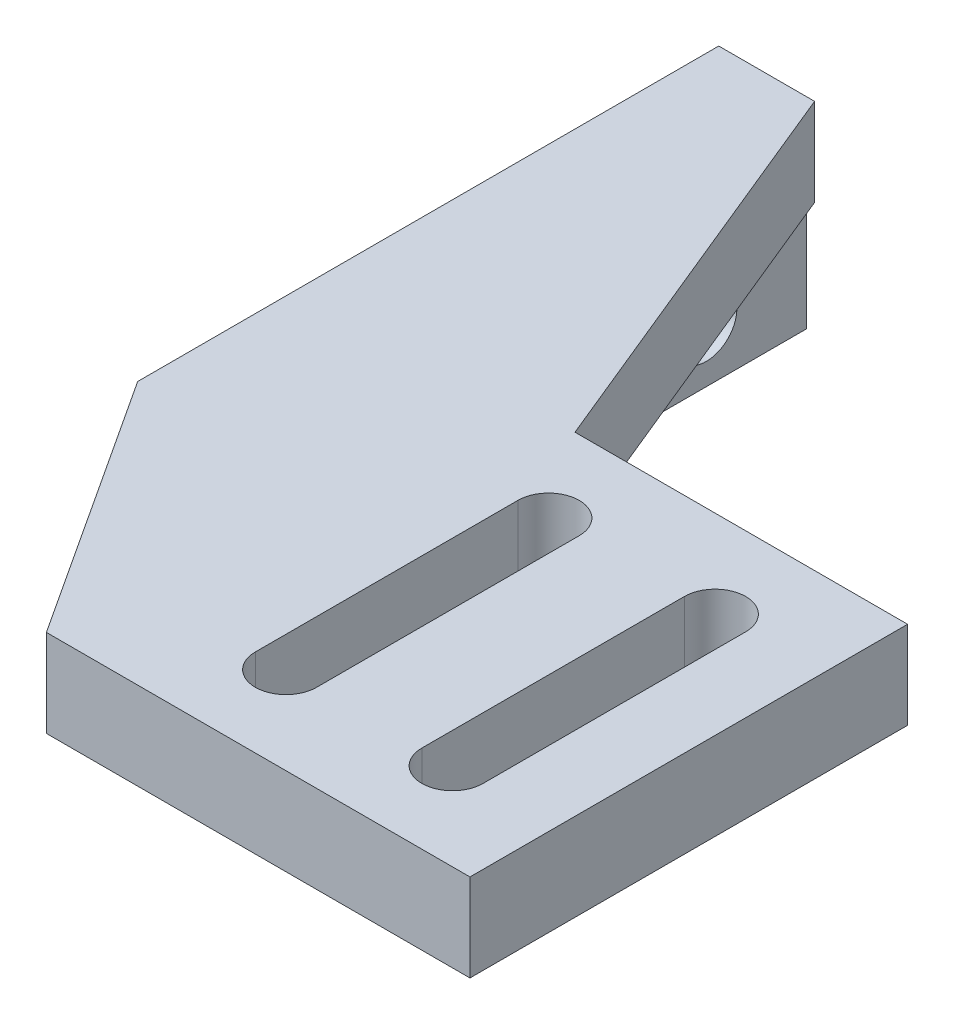
SolidWorks part; units mm, degrees
ref_plane "Piano frontale" through (0, 0, 0) normal (0, 0, 1) x (1, 0, 0)
ref_plane "Piano superiore" through (0, 0, 0) normal (0, 1, 0) x (1, 0, 0)
ref_plane "Piano destro" through (0, 0, 0) normal (1, 0, 0) x (0, 0, -1)
ref_plane "Piano1" through (0, 40, 0) normal (0, 1, 0) x (1, 0, 0)
sketch "Schizzo18" plane through (0, 40, 0) normal (0, 1, 0) x (1, 0, 0)
  line L0 (25, -16) -> (-9, -16)
  line L1 (25, -16) -> (25, 9)
  line L2 (25, 9) -> (6, 9)
  line L3 (-9, 32.2124) -> (-3.5247, 32.2124)
  line L4 (-9, -16) -> (-9, 32.2124)
  line L5 (-3.5247, 32.2124) -> (6, 9)
  line L6 (19, -16) -> (19, 9) construction
  line L7 (-9, -28.4145) -> (-9, 27.2974) construction
  line L8 (29.4558, 9) -> (-19.1855, 9) construction
  line L9 (25, -28.4145) -> (25, 27.2974) construction
  line L10 (29.4558, -16) -> (-19.1855, -16) construction
  line L11 (25, -11) -> (-9, -11) construction
  line L12 (25, 4) -> (-9, 4) construction
  line L13 (19, -11) -> (19, 4) construction
  line L14 (17.25, -11) -> (17.25, 4)
  line L15 (20.75, -11) -> (20.75, 4)
  line L16 (9.4906, -11) -> (9.4906, 4) construction
  line L17 (7.7406, -11) -> (7.7406, 4)
  line L18 (11.2406, -11) -> (11.2406, 4)
  arc A0 (17.25, -11) -> (20.75, -11) centre (19, -11) ccw
  arc A1 (20.75, 4) -> (17.25, 4) centre (19, 4) ccw
  arc A2 (7.7406, -11) -> (11.2406, -11) centre (9.4906, -11) ccw
  arc A3 (11.2406, 4) -> (7.7406, 4) centre (9.4906, 4) ccw
  point P22 (19, -3.5)
  point P29 (9.4906, -3.5)
  dimension "D6" = 15
  dimension "D1" = 6
  dimension "D2" = 25
  dimension "D3" = 34
  dimension "D4" = 5
  dimension "D5" = 15
extrude "Estrusione-Estrusione8" add sketch "Schizzo18" along normal blind 5 separate body
sketch "Schizzo19" plane through (0, 40, 0) normal (0, -1, 0) x (1, 0, 0)
  line L0 (-3.5247, -32.2124) -> (-9, -32.2124) construction
  line L1 (-9, 16) -> (-4, 16)
  line L2 (-9, 16) -> (-9, -32.2124)
  line L3 (-9, -32.2124) -> (-4, -32.2124)
  line L4 (-4, 16) -> (-4, -32.2124)
  dimension "D1" = 5
extrude "Estrusione-Estrusione9" add sketch "Schizzo19" along normal blind 6.5
sketch "Schizzo20" plane through (-9, 0, 0) normal (-1, 0, 0) x (0, 0, 1)
  line L0 (3.5, 45) -> (3.5, 33.5) construction
  line L1 (11, 45) -> (-4, 45) construction
  line L2 (16, 33.5) -> (-32.2124, 33.5) construction
  line L3 (-21.5, 45) -> (-21.5, 33.5) construction
  line L4 (-26.5, 45) -> (-26.5, 33.5) construction
  line L13 (-16.5, 45) -> (-16.5, 33.5) construction
  line L14 (-23.6103, 33.5) -> (25.3232, 33.5) construction
  line L15 (-23.6103, 36.5) -> (25.3232, 36.5) construction
  circle A0 centre (-26.5, 36.5) radius 1.75
  circle A1 centre (-16.5, 36.5) radius 1.75
  dimension "D1" = 25
  dimension "D2" = 5
  dimension "D3" = 5
  dimension "D4" = 3
extrude "Taglio-Estrusione9" cut sketch "Schizzo20" against normal blind 6
sketch "Schizzo21" plane through (-9, 0, 0) normal (-1, 0, 0) x (0, 0, 1)
  line L0 (16, 23.2712) -> (16, 48.2769) construction
  line L1 (1, 23.2712) -> (1, 48.2769) construction
  line L2 (16, 45) -> (16, 40.1473)
  dimension "D1" = 15
sketch "Schizzo24" plane through (0, 45, 0) normal (0, 1, 0) x (1, 0, 0)
  line L0 (-9, -16) -> (25, -16) construction
  line L2 (0.8051, -16) -> (-9, -0.979)
  line L3 (-9, 32.2124) -> (-9, -16) construction
  line L4 (-9, -0.979) -> (-9, -16)
  line L5 (-9, -16) -> (0.8051, -16)
extrude "Taglio-Estrusione13" cut sketch "Schizzo24" against normal blind 21
ref_plane "Piano2" through (0, 0, 0.979) normal (0, 0, 1) x (1, 0, 0)
sketch "Schizzo26" plane through (0, 0, 0.979) normal (0, 0, 1) x (1, 0, 0)
  line L0 (-9, 23.2712) -> (-9, 48.2769) construction
  line L1 (-4, 33.5) -> (-9, 33.5)
  line L2 (-4, 33.5) -> (-4, 40)
  line L3 (-4, 40) -> (-9, 40)
  line L4 (-9, 33.5) -> (-9, 40)
  line L5 (18.7, 40) -> (-18.7, 40) construction
extrude "Taglio-Estrusione15" cut sketch "Schizzo26" along normal blind 21
fillet "Raccordo1" radius 4 1 edges at (-6.5, 33.5, 0.979) type face fillet first side face at (-6.5, 36.75, 0.979) second side face at (-6.5, 33.5, -15.6167)
